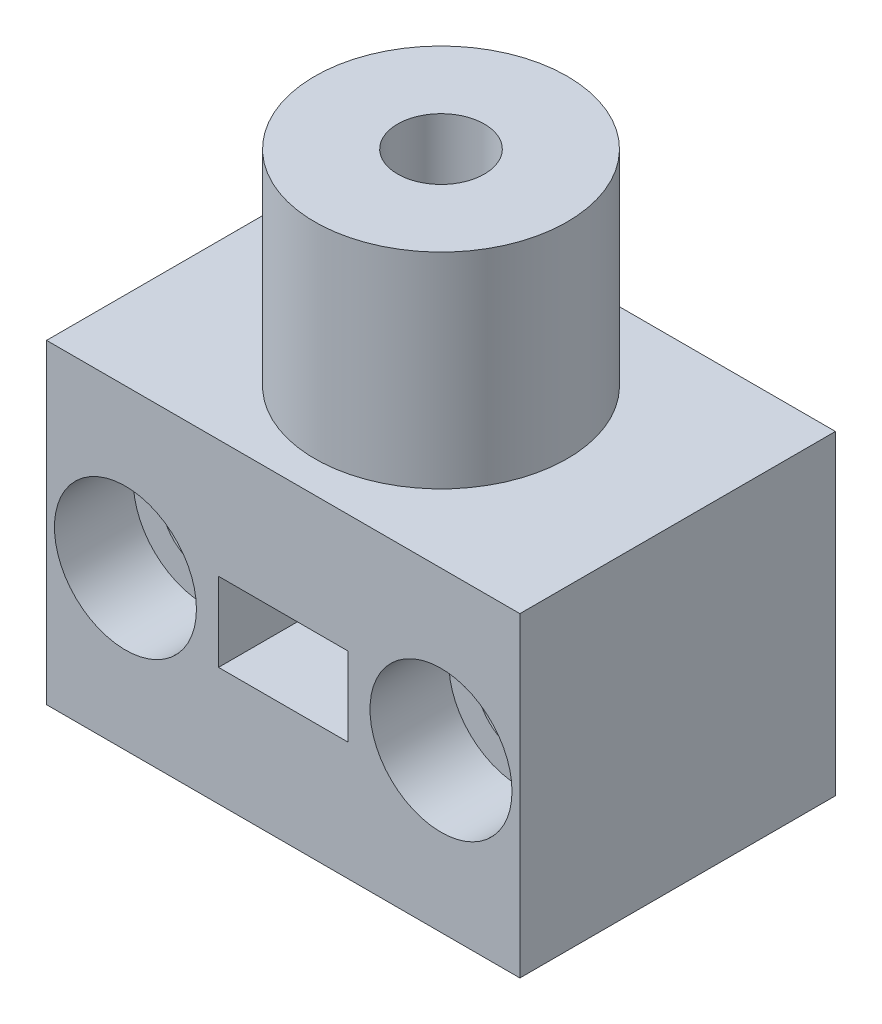
SolidWorks part; units mm, degrees
ref_plane "Front Plane" through (0, 0, 0) normal (0, 0, 1) x (1, 0, 0)
ref_plane "Top Plane" through (0, 0, 0) normal (0, 1, 0) x (1, 0, 0)
ref_plane "Right Plane" through (0, 0, 0) normal (1, 0, 0) x (0, 0, -1)
sketch "Sketch1" plane through (0, 0, 0) normal (0, 0, 1) x (1, 0, 0)
  line L1 (0, 0) -> (30, 0)
  line L2 (0, 0) -> (0, 20)
  line L3 (0, 20) -> (30, 20)
  line L4 (30, 0) -> (30, 20)
  dimension "D1" = 20
  dimension "D2" = 30
extrude "Boss-Extrude1" add sketch "Sketch1" along normal blind 20
sketch "Sketch2" plane through (0, 0, 20) normal (0, 0, 1) x (1, 0, 0)
  line L0 (30, 20) -> (0, 20) construction
  line L1 (0, 20) -> (0, 0) construction
  line L2 (30, 0) -> (30, 20) construction
  line L4 (10.9, 7.5) -> (19.1, 7.5)
  line L5 (10.9, 7.5) -> (10.9, 12.5)
  line L6 (10.9, 12.5) -> (19.1, 12.5)
  line L7 (19.1, 7.5) -> (19.1, 12.5)
  circle A0 centre (5, 10) radius 2.75
  circle A1 centre (25, 10) radius 2.75
  dimension "D1" = 5.5
  dimension "D2" = 5.5
  dimension "D3" = 10
  dimension "D4" = 10
  dimension "D5" = 5
  dimension "D6" = 5
  dimension "D7" = 5
  dimension "D8" = 8.2
  dimension "D9" = 10.9
  dimension "D10" = 7.5
extrude "Cut-Extrude1" cut sketch "Sketch2" against normal through all
sketch "Sketch3" plane through (0, 20, 0) normal (0, 1, 0) x (1, 0, 0)
  line L0 (0, -20) -> (0, 0) construction
  line L1 (30, 0) -> (0, 0) construction
  circle A0 centre (15, -10) radius 2.75
  dimension "D1" = 5.5
  dimension "D2" = 15
  dimension "D3" = 10
extrude "Cut-Extrude2" cut sketch "Sketch3" against normal through all
sketch "Sketch4" plane through (0, 7.5, 0) normal (0, 1, 0) x (1, 0, 0)
  line L0 (19.1, -7.5) -> (15.1, -5.1339)
  line L1 (19.1, 0) -> (19.1, -20) construction
  line L2 (15.1, -5.1339) -> (10.9, -7.5)
  line L3 (10.9, 0) -> (10.9, -20) construction
  line L8 (10.9, -20) -> (19.1, -20)
  line L9 (19.1, -20) -> (19.1, 0)
  line L10 (19.1, 0) -> (10.9, 0)
  line L11 (10.9, 0) -> (10.9, -20)
  line L13 (19.1, -7.5) -> (19.1, 0)
  line L14 (19.1, 0) -> (10.9, 0)
  line L15 (10.9, 0) -> (10.9, -7.5)
  point P4 (10.9, -10)
  point P9 (19.1, -10)
  dimension "D1" = 2.5
  dimension "D2" = 2.5
  dimension "D3" = 120
  dimension "D4" = 4
  dimension "D5" = 0
extrude "Boss-Extrude2" add sketch "Sketch4" along normal up to next
sketch "Sketch5" plane through (0, 0, 0) normal (0, 0, -1) x (-1, 0, 0)
  line L0 (-30, 20) -> (0, 20) construction
  line L1 (-19, 7) -> (-11, 7)
  line L2 (-19, 7) -> (-19, 13)
  line L3 (-19, 13) -> (-11, 13)
  line L4 (-11, 7) -> (-11, 13)
  line L5 (-30, 0) -> (-30, 20) construction
  dimension "D1" = 6
  dimension "D2" = 8
  dimension "D3" = 7
  dimension "D4" = 11
extrude "Boss-Extrude3" add sketch "Sketch5" along normal blind 3
sketch "Sketch6" plane through (0, 0, 20) normal (0, 0, 1) x (1, 0, 0)
  circle A0 centre (5, 10) radius 4.5
  circle A1 centre (25, 10) radius 4.5
  dimension "D1" = 9
  dimension "D2" = 9
extrude "Cut-Extrude3" cut sketch "Sketch6" against normal blind 5
sketch "Sketch7" plane through (0, 20, 0) normal (0, 1, 0) x (1, 0, 0)
  circle A0 centre (15, -10) radius 2.75
  circle A1 centre (15, -10) radius 8
  dimension "D1" = 16
extrude "Boss-Extrude4" add sketch "Sketch7" along normal blind 13
